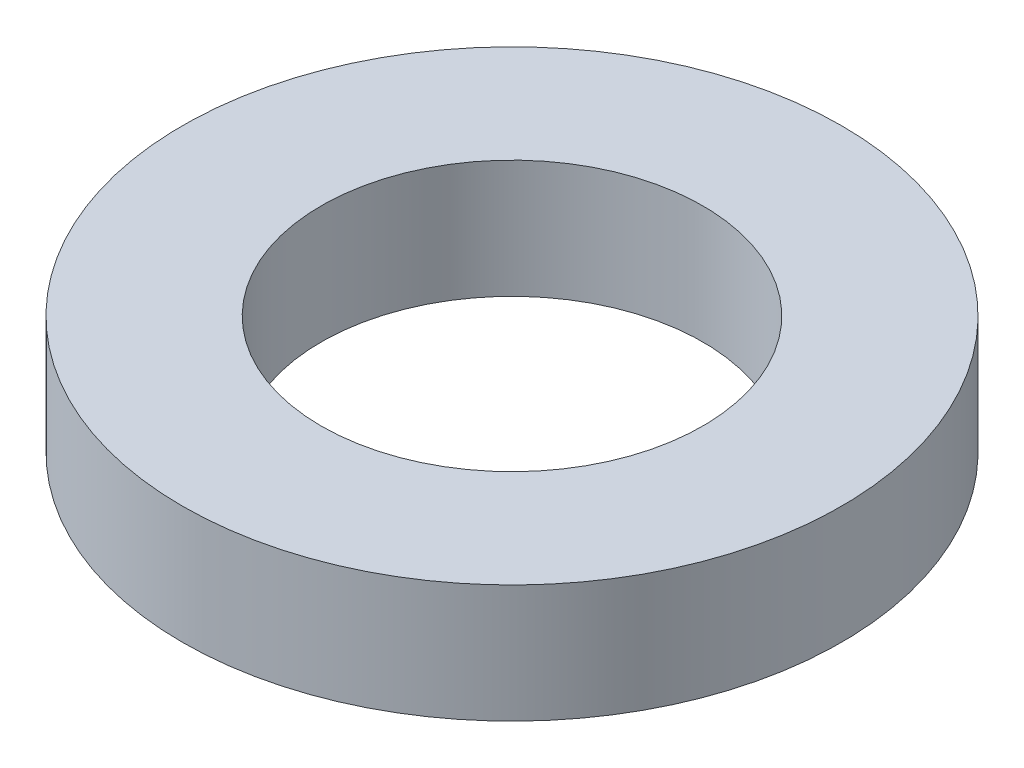
SolidWorks part; units mm, degrees
ref_plane "Front Plane" through (0, 0, 0) normal (0, 0, 1) x (1, 0, 0)
ref_plane "Top Plane" through (0, 0, 0) normal (0, 1, 0) x (1, 0, 0)
ref_plane "Right Plane" through (0, 0, 0) normal (1, 0, 0) x (0, 0, -1)
sketch "Sketch1" plane through (0, 0, 0) normal (0, 1, 0) x (1, 0, 0)
  circle A0 centre (0, 0) radius 47.5
  dimension "FLANGE_OD" = 95
extrude "Boss-Extrude1" add sketch "Sketch1" along normal blind 17
sketch "Sketch2" plane through (0, 0, 0) normal (0, 1, 0) x (1, 0, 0)
  circle A0 centre (0, 0) radius 27.5
  dimension "BORE_D" = 55
extrude "Cut-Extrude1" cut sketch "Sketch2" along normal through all
sketch "Sketch3" plane through (0, 17, 0) normal (0, 1, 0) x (1, 0, 0)
  circle A0 centre (0, 0) radius 16.9449 construction
  circle A1 centre (-16.9449, 0) radius 3.2954
  dimension "BOLT_D" = 6.5909
  dimension "BOLT_PCD" = 33.8899
extrude "Cut-Extrude2" cut sketch "Sketch3" against normal blind 14.3331 rebuild error yes
pattern_circular "CirPattern1" count 6 over 360 rebuild error yes
